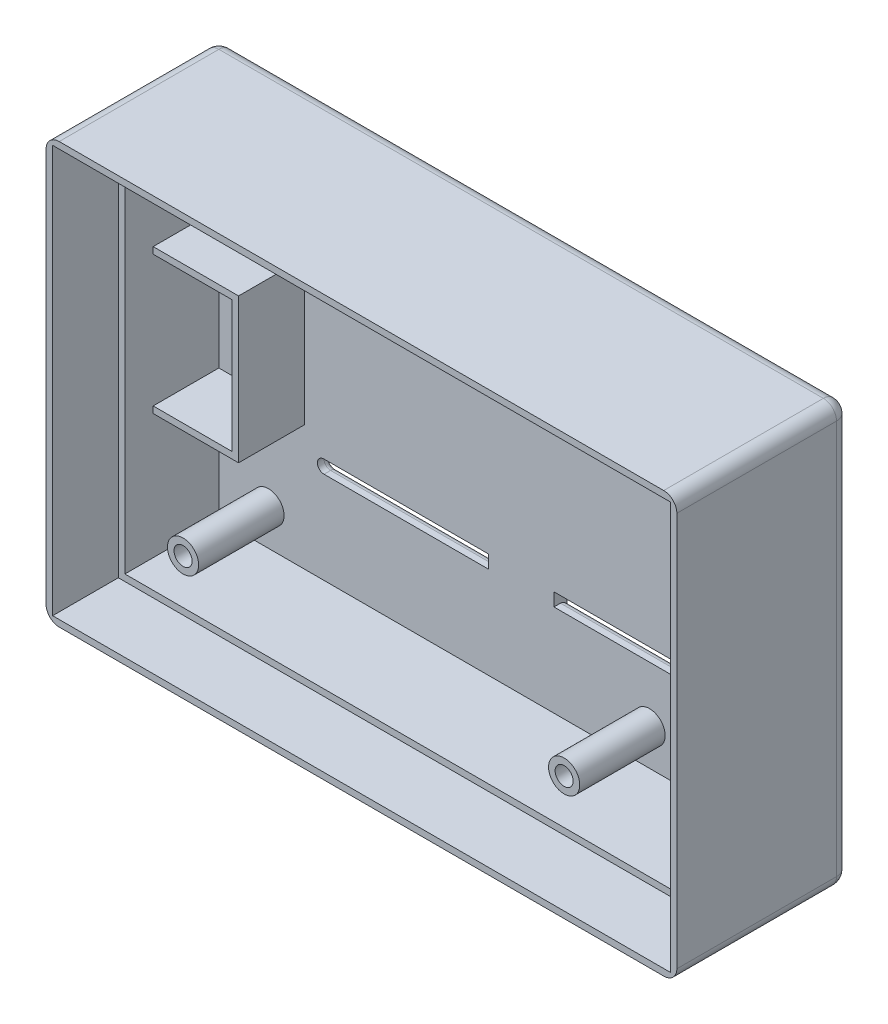
SolidWorks part; units mm, degrees
ref_plane "Front Plane" through (0, 0, 0) normal (0, 0, 1) x (1, 0, 0)
ref_plane "Top Plane" through (0, 0, 0) normal (0, 1, 0) x (1, 0, 0)
ref_plane "Right Plane" through (0, 0, 0) normal (1, 0, 0) x (0, 0, -1)
sketch "Sketch1" plane through (0, 0, 0) normal (0, 0, 1) x (1, 0, 0)
  line L0 (30, 23.1458) -> (5, 23.1458) construction
  line L1 (-46, 30) -> (46, 30)
  line L2 (-46, 30) -> (-46, -30)
  line L3 (-46, -30) -> (46, -30)
  line L4 (46, 30) -> (46, -30)
  line L5 (-46, 30) -> (-21.4667, 14) construction
  line L6 (-46, -30) -> (46, 30) construction
  line L7 (-30, 15) -> (-30, 0) construction
  line L8 (-30, 0) -> (-30, -15) construction
  line L9 (0, 0) -> (46, -30) construction
  line L10 (30, 17.9514) -> (30, -23.4514) construction
  line L11 (-30, 15) -> (-5, 15) construction
  line L12 (-30, 16) -> (-5, 16)
  line L13 (-30, 14) -> (-5, 14)
  line L14 (-30, -15) -> (-5, -15) construction
  line L15 (-30, -14) -> (-5, -14)
  line L16 (-30, -16) -> (-5, -16)
  line L17 (5, -14) -> (5, -16)
  line L18 (-30, 23.1458) -> (-5, 23.1458) construction
  line L19 (30, 15) -> (30, 23.1458) construction
  line L20 (-30, 15) -> (-30, 23.1458) construction
  line L21 (5, 16) -> (5, 14)
  line L22 (-5, 16) -> (-5, 14)
  line L23 (5, 16) -> (30, 16)
  line L24 (5, 15) -> (30, 15) construction
  line L25 (5, 14) -> (30, 14)
  line L26 (-5, -14) -> (-5, -16)
  line L27 (5, -14) -> (30, -14)
  line L28 (5, -15) -> (30, -15) construction
  line L29 (5, -16) -> (30, -16)
  arc A0 (-30, 16) -> (-30, 14) centre (-30, 15) ccw
  arc A1 (30, 14) -> (30, 16) centre (30, 15) ccw
  arc A2 (-30, -14) -> (-30, -16) centre (-30, -15) ccw
  arc A3 (30, -16) -> (30, -14) centre (30, -15) ccw
  point P0 (0, 0)
  point P13 (0, 15)
  point P19 (0, -15)
  dimension "D1" = 92
  dimension "D2" = 60
  dimension "D3" = 15
  dimension "D4" = 15
  dimension "D5" = 30
  dimension "D6" = 25
  dimension "D7" = 2
  dimension "D8" = 2
  dimension "D9" = 25
extrude "Boss-Extrude1" add sketch "Sketch1" along normal blind 2
sketch "Sketch2" plane through (0, 0, 2) normal (0, 0, 1) x (1, 0, 0)
  line L1 (-46, 30) -> (46, 30)
  line L2 (-46, 30) -> (-46, -30)
  line L3 (-46, -30) -> (46, -30)
  line L4 (46, 30) -> (46, -30)
  line L5 (-46, 32) -> (46, 32)
  line L7 (48, 30) -> (48, -30.0404)
  line L9 (46.0404, -32) -> (-46, -32)
  line L12 (-48, -30) -> (-48, 30)
  arc A0 (-46, -32) -> (-48, -30) centre (-46, -30) cw
  arc A1 (-46, 32) -> (-48, 30) centre (-46, 30) ccw
  arc A2 (46, 32) -> (48, 30) centre (46, 30) cw
  arc A3 (48, -30.0404) -> (46.0404, -32) centre (46.0404, -30.0404) cw
  dimension "D1" = 2
  dimension "D2" = 2
  dimension "D3" = 2
  dimension "D4" = 2
extrude "Boss-Extrude2" add sketch "Sketch2" along normal blind 24.3 and the other way blind 2 separate body
sketch "Sketch3" plane through (0, 0, 2) normal (0, 0, 1) x (1, 0, 0)
  line L0 (-54.6097, 0) -> (61.6107, 0) construction
  line L1 (0, 45.6724) -> (0, -40.7225) construction
  line L2 (-38.4514, 0) -> (-38.4514, -24.5) construction
  line L3 (-38.4514, 0) -> (-38.4514, 24.5) construction
  line L4 (-38.4514, 24.5) -> (19.5486, 24.5) construction
  line L5 (19.5486, 24.5) -> (19.5486, -24.5) construction
  circle A0 centre (-38.4514, 24.5) radius 1.375
  circle A1 centre (19.5486, 24.5) radius 1.375
  circle A2 centre (19.5486, -24.5) radius 1.375
  circle A3 centre (-38.4514, -24.5) radius 1.375
  dimension "D4" = 2.75
  dimension "D5" = 2.75
  dimension "D6" = 2.75
  dimension "D7" = 2.75
  dimension "D1" = 24.5
  dimension "D2" = 24.5
  dimension "D3" = 58
extrude "Cut-Extrude1" cut sketch "Sketch3" against normal blind 30
sketch "Sketch4" plane through (0, 0, 2) normal (0, 0, 1) x (1, 0, 0)
  line L0 (-59.6206, 0) -> (69.0421, 0) construction
  line L1 (47, -11) -> (47, 11) construction
  line L2 (-46, -10) -> (-34, -10)
  line L3 (-46, -10) -> (-46, 10)
  line L4 (-46, 10) -> (-34, 10)
  line L5 (-34, -10) -> (-34, 10)
  line L6 (-46, -10) -> (-34, 10) construction
  line L7 (-46, 10) -> (-34, -10) construction
  line L8 (34, -10) -> (46, -10)
  line L9 (34, -10) -> (34, 10)
  line L10 (34, 10) -> (46, 10)
  line L11 (46, -10) -> (46, 10)
  line L12 (34, -10) -> (46, 10) construction
  line L13 (34, 10) -> (46, -10) construction
  line L14 (33, 11) -> (46, 11)
  line L15 (46, 11) -> (46, 10)
  line L16 (-46, 30) -> (-46, -30) construction
  line L17 (46, -30) -> (46, 30) construction
  line L18 (-46, 11) -> (-33, 11)
  line L19 (-33, -11) -> (-33, 11)
  line L20 (-46, -11) -> (-33, -11)
  line L21 (46, 10) -> (44.0427, 9.8768)
  line L22 (-46, 10) -> (-46, 11)
  line L23 (-46, -10) -> (-46, -11)
  line L24 (-47, -11) -> (-33, -11) construction
  line L25 (-47, -11) -> (-47, 11) construction
  line L26 (-47, 11) -> (-33, 11) construction
  line L27 (33, -11) -> (46, -11)
  line L28 (46, -11) -> (46, -10)
  line L29 (33, -11) -> (33, 11)
  line L30 (33, 11) -> (47, 11) construction
  line L31 (33, -11) -> (47, -11) construction
  point P3 (-40, 0)
  point P8 (40, 0)
  line M12 (46, -30) -> (46, 30)
  line M14 (-46, 30) -> (-46, -30)
  dimension "D1" = 20
  dimension "D2" = 12
  dimension "D3" = 20
  dimension "D4" = 12
  dimension "D5" = 1
  dimension "D6" = 1
extrude "Boss-Extrude3" add sketch "Sketch4" along normal blind 10 contours L20 L19 L18 L4 L5 L2 M14 | L29 L27 L8 L9 L10 L14 M12 region at (-40, -10.2555, 2) region at (40, -10.2555, 2)
sketch "Sketch5" plane through (0, 0, 2) normal (0, 0, 1) x (1, 0, 0)
  circle A0 centre (-38.4514, 24.5) radius 1.375
  circle A1 centre (-38.4514, 24.5) radius 2.375
  circle A2 centre (19.5486, 24.5) radius 1.375
  circle A3 centre (19.5486, 24.5) radius 2.375
  circle A4 centre (-38.4514, -24.5) radius 1.375
  circle A5 centre (-38.4514, -24.5) radius 2.375
  circle A6 centre (19.5486, -24.5) radius 1.375
  circle A7 centre (19.5486, -24.5) radius 2.375
  dimension "D1" = 4.75
  dimension "D2" = 4.75
  dimension "D3" = 4.75
  dimension "D4" = 4.75
extrude "Boss-Extrude4" add sketch "Sketch5" along normal blind 13
sketch "Sketch6" plane through (0, 0, 26.3) normal (0, 0, 1) x (1, 0, 0)
  line L0 (-46, -30) -> (46, -30) construction
  line L1 (-46, 30) -> (46, 30)
  line L2 (-46, 30) -> (-46, -30)
  line L3 (-46, -30) -> (46, -30)
  line L4 (46, 30) -> (46, -30)
  line L5 (-47, -31) -> (47, -31)
  line L6 (47, 31) -> (47, -31)
  line L7 (-47, 31) -> (47, 31)
  line L8 (-47, 31) -> (-47, -31)
  dimension "D1" = 1
extrude "Cut-Extrude2" cut sketch "Sketch6" against normal blind 10
sketch "Sketch8" plane through (0, 0, 12) normal (0, 0, 1) x (1, 0, 0)
  line L1 (33, 11) -> (46, 11)
  line L2 (33, 11) -> (33, -11)
  line L3 (33, -11) -> (46, -11)
  line L4 (46, 11) -> (46, -11)
extrude "Cut-Extrude3" cut sketch "Sketch8" against normal blind 10
fillet "Fillet1" radius 2 8 edges at (-47.4142, 31.4142, 0) (-48, 0, 0) (-47.4142, -31.4142, 0) (0.0202, -32, 0) (47.426, -31.426, 0) (48, -0.0202, 0) (47.4142, 31.4142, 0) (0, 32, 0)
fillet "Fillet2" radius 1 12 edges at (-17.5, -16, 0) (-31, -15, 0) (17.5, -16, 0) (31, -15, 0) (-17.5, 14, 0) (-31, 15, 0) (17.5, 14, 0) (31, 15, 0) (-17.5, -14, 0) (17.5, -14, 0) (-17.5, 16, 0) (17.5, 16, 0)
